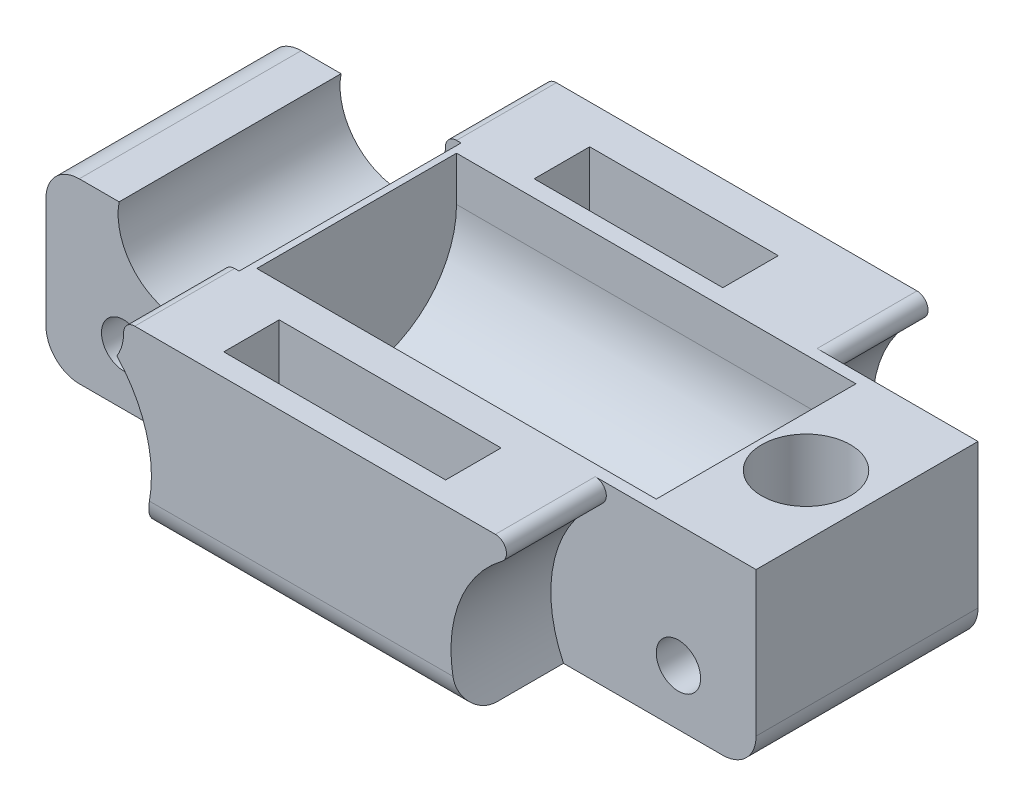
SolidWorks part; units mm, degrees
ref_plane "Front Plane" through (0, 0, 0) normal (0, 0, 1) x (1, 0, 0)
ref_plane "Top Plane" through (0, 0, 0) normal (0, 1, 0) x (1, 0, 0)
ref_plane "Right Plane" through (0, 0, 0) normal (1, 0, 0) x (0, 0, -1)
sketch "Sketch1" plane through (0, 0, 0) normal (0, 1, 0) x (1, 0, 0)
  line L1 (-32, 19) -> (32, 19)
  line L2 (-32, 19) -> (-32, -19)
  line L3 (-32, -19) -> (32, -19)
  line L4 (32, 19) -> (32, -19)
  line L5 (-32, 19) -> (32, -19) construction
  line L6 (-32, -19) -> (32, 19) construction
  point P0 (0, 0)
  dimension "D1" = 64
  dimension "D2" = 38
extrude "Boss-Extrude1" add sketch "Sketch1" along normal blind 16
sketch "Sketch2" plane through (0, 0, 0) normal (0, 0, 1) x (1, 0, 0)
  point P0 (-25, 5)
  point P1 (25, 5)
  dimension "D1" = 50
  dimension "D2" = 25
  dimension "D3" = 5
sketch "Sketch3" plane through (0, 0, 0) normal (0, 0, 1) x (1, 0, 0)
  line L0 (25, 16.5) -> (36.5, 16.5)
  line L1 (36.5, 16.5) -> (36.5, 5)
  line L2 (36.5, 5) -> (36.5, -6.5)
  line L3 (36.5, -6.5) -> (25, -6.5)
  line L4 (-25, -6.5) -> (-36.5, -6.5)
  line L5 (-36.5, -6.5) -> (-36.5, 16.5)
  line L6 (-36.5, 16.5) -> (-25, 16.5)
  circle A0 centre (-25, 5) radius 11.5
  circle A1 centre (25, 5) radius 11.5
  dimension "D1" = 23
extrude "Cut-Extrude2" cut sketch "Sketch3" along normal blind 10 from offset 10 contours A1 L3 L2 | A1 | A1 L1 L0 | A0 | A0 L5 L4 | A0 L6 L5 region at (33.9313, 13.9313, 0) region at (25, 5, 0) region at (33.9313, -3.9313, 0) region at (-25, 5, 0) region at (-33.9313, -3.9313, 0) region at (-33.9313, 13.9313, 0)
mirror "Mirror1" about plane through (0, 0, 0) normal (0, 0, 1) of "Cut-Extrude2"
sketch "Sketch5" plane through (0, 0, 0) normal (0, 0, 1) x (1, 0, 0)
  circle A0 centre (25, 5) radius 2
  circle A1 centre (-25, 5) radius 2
  dimension "D1" = 4
extrude "Cut-Extrude3" cut sketch "Sketch5" against normal through all both and the other way through all
sketch "Sketch4" plane through (0, 0, 0) normal (1, 0, 0) x (0, 0, -1)
  line L0 (-9, 12) -> (-9, 23.0528)
  line L1 (-9, 23.0528) -> (9, 23.0528)
  line L2 (9, 23.0528) -> (9, 12)
  circle A0 centre (0, 12) radius 9
  dimension "D1" = 18
  dimension "D2" = 12
extrude "Battery" add sketch "Sketch4" along normal blind 22 and the other way blind 14 separate body contours A0 | A0 L2 L1 L0 region at (0, 17.5264, 8.7888) region at (0, 12, 0)
combine bodies "Combine1" operation type subtract main body 106 bodies to subtract 104
sketch "Sketch13" plane through (0, 16, 0) normal (0, 1, 0) x (1, 0, 0)
  circle A0 centre (26.5, 0) radius 4
  dimension "D1" = 8
  dimension "D2" = 26.5
extrude "MountHole" cut sketch "Sketch13" against normal blind 6
sketch "Sketch6" plane through (0, 0, 0) normal (0, 1, 0) x (1, 0, 0)
  line L1 (8.5, 10.5) -> (-8.5, 10.5)
  line L2 (8.5, 10.5) -> (8.5, 15.5)
  line L3 (8.5, 15.5) -> (-8.5, 15.5)
  line L4 (-8.5, 10.5) -> (-8.5, 15.5)
  line L5 (8.5, 10.5) -> (-8.5, 15.5) construction
  line L6 (8.5, 15.5) -> (-8.5, 10.5) construction
  point P0 (0, 13)
  dimension "D1" = 17
  dimension "D2" = 5
  dimension "D3" = 13
extrude "Charger" cut sketch "Sketch6" along normal up to next from offset 3
sketch "Sketch7" plane through (0, 0, 0) normal (0, -1, 0) x (1, 0, 0)
  line L1 (6, -17) -> (-6, -17)
  line L2 (6, -17) -> (6, -9)
  line L3 (6, -9) -> (-6, -9)
  line L4 (-6, -17) -> (-6, -9)
  line L5 (6, -17) -> (-6, -9) construction
  line L6 (6, -9) -> (-6, -17) construction
  point P0 (0, -13)
  dimension "D1" = 12
  dimension "D2" = 8
extrude "MicroUSB" cut sketch "Sketch7" against normal blind 3
fillet "Fillet1" radius 1.5 2 edges at (0, 3, -17) (0, 3, -9)
sketch "Sketch8" plane through (0, 0, 0) normal (0, 0, 1) x (1, 0, 0)
  circle A0 centre (-20, 15) radius 5.5
  dimension "D1" = 11
  dimension "D2" = 20
  dimension "D3" = 15
extrude "Motor" cut sketch "Sketch8" against normal mid plane 20
sketch "Sketch9" plane through (0, 0, 0) normal (0, 0, 1) x (1, 0, 0)
  circle A0 centre (-20, 15) radius 4
  point P3 (-21.1758, 19.2117)
extrude "Gear" cut sketch "Sketch9" against normal through all both and the other way through all
fillet "Fillet_3mm" radius 3 5 edges at (-32, 16, 0) (0, 0, 19) (0, 0, -19) (32, 0, 0) (-32, 0, 0)
fillet "Fillet_1mm" radius 1 4 edges at (-16.127, 16, 14.5) (-16.127, 16, -14.5) (21.6459, 16, 14.5) (21.6459, 16, -14.5)
sketch "Sketch10" plane through (0, 16, 0) normal (0, 1, 0) x (1, 0, 0)
  line L0 (-15, -19) -> (17.5, -19) construction
  line L1 (-8.983, -12) -> (11.017, -12)
  line L2 (-8.983, -12) -> (-8.983, -17)
  line L3 (-8.983, -17) -> (11.017, -17)
  line L4 (11.017, -12) -> (11.017, -17)
  line L5 (-8.983, -12) -> (11.017, -17) construction
  line L6 (-8.983, -17) -> (11.017, -12) construction
  point P0 (1.017, -14.5)
  dimension "D1" = 20
  dimension "D2" = 5
  dimension "D3" = 2
extrude "ControlBoard" cut sketch "Sketch10" against normal blind 12
hole_wizard "CSK for M3 Flat Head Machine Screw1" positions "Sketch11" profile "Sketch12" countersink size "M3" standard "ANSI Metric"
sketch "Sketch11" plane through (0, 0, 0) normal (0, -1, 0) x (-1, 0, 0)
  point P0 (-26.5, 0)
  point P3 (0, 0)
  point P5 (0, 0)
sketch "Sketch12" plane through (26.5, 0, 0) normal (1, 0, 0) x (0, 0, -1)
  line L0 (0, 0) -> (0, 11.0815)
  line L1 (0, 11.0815) -> (1.8, 10)
  line L2 (1.8, 10) -> (1.8, 1.35)
  line L3 (1.8, 1.35) -> (3.15, 0)
  line L5 (3.15, 0) -> (0, 0)
  line L6 (-1.8, 1.35) -> (-3.15, 0) construction
  line L10 (0, 11.0815) -> (-1.8, 10) construction
  line L11 (0, -6.35) -> (0, 107.95) construction
  dimension "Hole Dia." = 3.6
  dimension "Hole Depth" = 10
  dimension "Near C'Sink Dia." = 6.3
  dimension "Near C'Sink Angle" = 90
  dimension "Drill Angle" = 118
